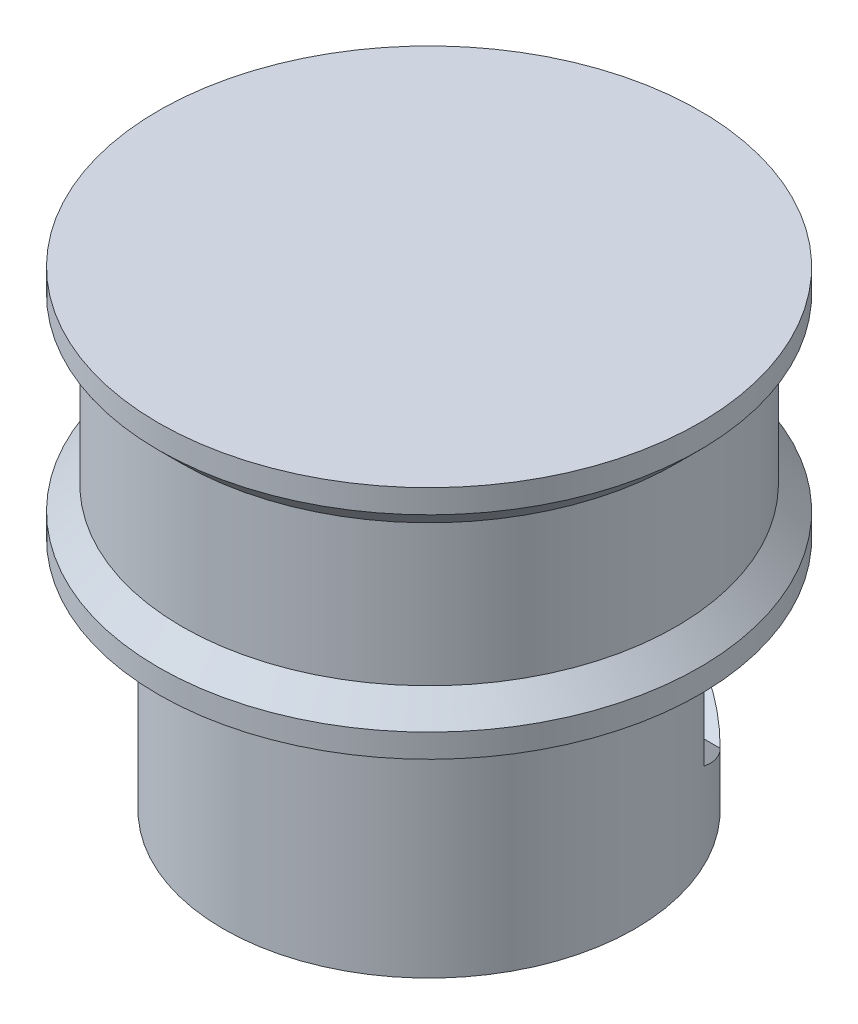
SolidWorks part; units mm, degrees
ref_plane "Front Plane" through (0, 0, 0) normal (0, 0, 1) x (1, 0, 0)
ref_plane "Top Plane" through (0, 0, 0) normal (0, 1, 0) x (1, 0, 0)
ref_plane "Right Plane" through (0, 0, 0) normal (1, 0, 0) x (0, 0, -1)
sketch "Sketch1" plane through (0, 0, 0) normal (0, 1, 0) x (1, 0, 0)
  circle A0 centre (0, 0) radius 11.1125
  dimension "D1" = 22.225
extrude "Boss-Extrude1" add sketch "Sketch1" along normal mid plane 25.4
sketch "Sketch2" plane through (0, 12.7, 0) normal (0, 1, 0) x (1, 0, 0)
  circle A0 centre (0, 0) radius 4
  dimension "D1" = 8
extrude "Cut-Extrude1" cut sketch "Sketch2" against normal up to surface (12.7 mm away) up to plane "Top Plane"
sketch "Sketch3" plane through (0, -12.7, 0) normal (0, -1, 0) x (1, 0, 0)
  circle A0 centre (0, 0) radius 4.7625
  dimension "D1" = 9.525
extrude "Cut-Extrude2" cut sketch "Sketch3" against normal up to surface (12.7 mm away) up to plane "Top Plane"
sketch "Sketch4" plane through (0, 12.7, 0) normal (0, 1, 0) x (1, 0, 0)
  line L0 (-1, 3.873) -> (-1, 11.0674)
  line L1 (1, 11.0674) -> (1, 3.873)
  circle A0 centre (0, 0) radius 4 construction
  circle A1 centre (0, 0) radius 11.1125
  arc A2 (1, 11.0674) -> (-1, 11.0674) centre (0, 0) ccw
  arc A3 (1, 3.873) -> (-1, 3.873) centre (0, 0) ccw
  dimension "D2" = 2
  dimension "D1" = 0
extrude "Cut-Extrude3" cut sketch "Sketch4" against normal up to next
ref_plane "Plane1" through (7, 0, 0) normal (-1, 0, 0) x (0, 0, 1)
sketch "Sketch5" plane through (7, 0, 0) normal (1, 0, 0) x (0, 0, -1)
  line L0 (7.8619, -6.35) -> (7.8619, 6.35) construction
  line L1 (7.8619, 2.8859) -> (10.8619, 4.6179)
  line L2 (10.8619, 4.6179) -> (10.8619, 8.0821)
  line L3 (10.8619, 8.0821) -> (7.8619, 9.8141)
  line L4 (7.8619, 9.8141) -> (4.8619, 8.0821)
  line L5 (4.8619, 8.0821) -> (4.8619, 4.6179)
  line L6 (4.8619, 4.6179) -> (7.8619, 2.8859)
  line L7 (7.8619, -9.8141) -> (10.8619, -8.0821)
  line L8 (10.8619, -8.0821) -> (10.8619, -4.6179)
  line L9 (10.8619, -4.6179) -> (7.8619, -2.8859)
  line L10 (7.8619, -2.8859) -> (4.8619, -4.6179)
  line L11 (4.8619, -4.6179) -> (4.8619, -8.0821)
  line L12 (4.8619, -8.0821) -> (7.8619, -9.8141)
  line L13 (11.0674, -12.7) -> (4.6563, -12.7) construction
  circle A0 centre (7.8619, 6.35) radius 3 construction
  circle A1 centre (7.8619, -6.35) radius 3 construction
  point P9 (7.8619, 0)
  point P21 (7.8619, -12.7)
  dimension "D1" = 6
  dimension "D2" = 6.35
extrude "Cut-Extrude4" cut sketch "Sketch5" against normal blind 4 and the other way up to next
hole_wizard "M3 Clearance Hole1" positions "Sketch6" profile "Sketch7" hole size "M3" standard "ANSI Metric" end condition through all
sketch "Sketch6" plane through (3, 0, 0) normal (1, 0, 0) x (0, 0, -1)
  point P0 (7.8619, 6.35)
  point P3 (7.8619, -6.35)
sketch "Sketch7" plane through (3, 6.35, -7.8619) normal (0, 1, 0) x (0, 0, -1)
  line L0 (0, 0) -> (0, 14.1125)
  line L1 (0, 14.1125) -> (1.7, 14.1125)
  line L2 (1.7, 14.1125) -> (1.7, 0)
  line L5 (1.7, 0) -> (0, 0)
  line L11 (0, -6.35) -> (0, 107.95) construction
  dimension "Thru Hole Dia." = 3.4
  dimension "Thru Hole Depth" = 14.1125
ref_plane "Plane2" through (-3, 0, 0) normal (1, 0, 0) x (0, 0, -1)
sketch "Sketch9" plane through (-3, 0, 0) normal (1, 0, 0) x (0, 0, -1)
  circle A0 centre (7.8619, 6.35) radius 3.5
  circle A1 centre (7.8619, -6.35) radius 3.5
  dimension "D1" = 7
extrude "Cut-Extrude5" cut sketch "Sketch9" against normal up to next
split "Split1" bodies to split 107 resulting bodies 108 109 split by face at (0, 0, 0.0583)
delete or keep bodies "Body-Delete/Keep 1" type delete bodies bodies 109
sketch "Sketch10" plane through (0, 0, 0) normal (0, 1, 0) x (1, 0, 0)
  circle A0 centre (0, 0) radius 14.605
  dimension "D1" = 29.21
extrude "Boss-Extrude2" add sketch "Sketch10" along normal blind 12.7
sketch "Sketch11" plane through (0, 12.7, 0) normal (0, 1, 0) x (1, 0, 0)
  circle A0 centre (0, 0) radius 14.605 construction
  circle A1 centre (0, 0) radius 14.605
  circle A2 centre (0, 0) radius 13.335
  dimension "D1" = 1.27
extrude "Cut-Extrude6" cut sketch "Sketch11" against normal offset from surface (7.62 mm away) 2.54 from offset 2.54 up to face at (0, 0, 14.605) offset against normal yes
chamfer "Chamfer1" distance 1.27 angle 45 2 edges at (0, 10.16, 14.605) (0, 2.54, 14.605)
